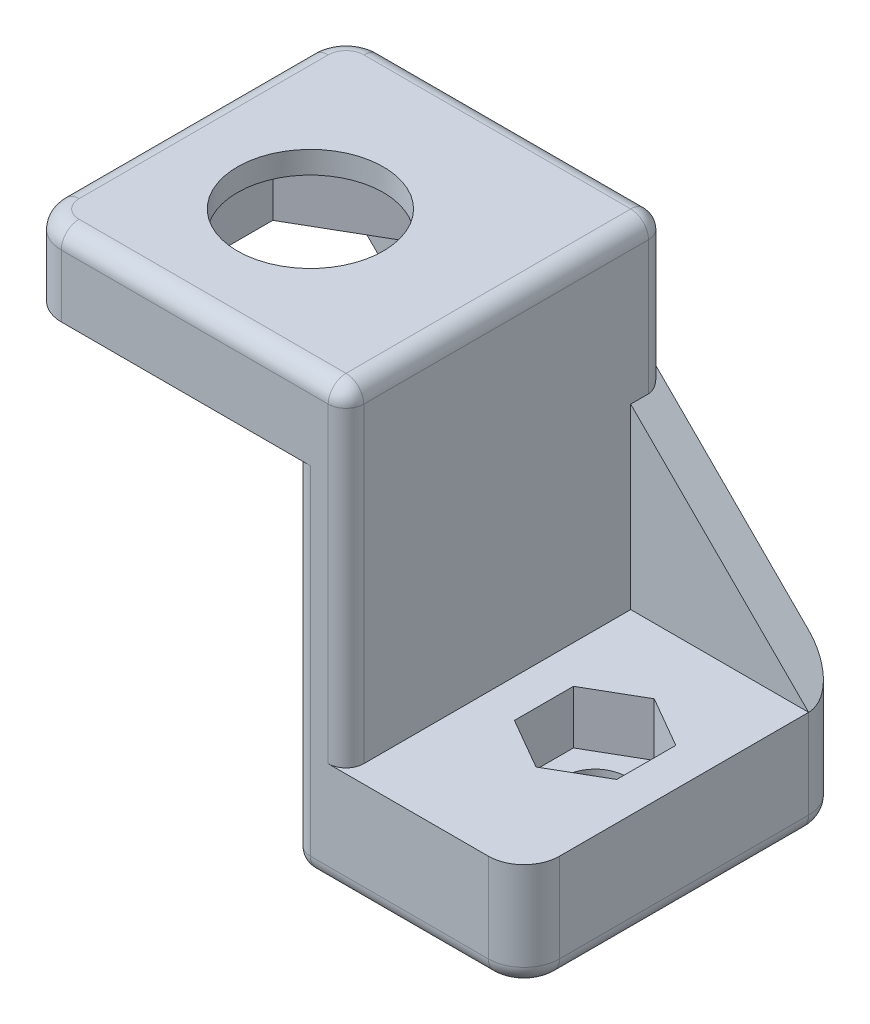
SolidWorks part; units mm, degrees
ref_plane "Front Plane" through (0, 0, 0) normal (0, 0, 1) x (1, 0, 0)
ref_plane "Top Plane" through (0, 0, 0) normal (0, 1, 0) x (1, 0, 0)
ref_plane "Right Plane" through (0, 0, 0) normal (1, 0, 0) x (0, 0, -1)
sketch "Sketch1" plane through (0, 0, 0) normal (0, 0, 1) x (1, 0, 0)
  line L0 (0, 0) -> (0, 40)
  line L1 (0, 40) -> (-30, 40)
  line L2 (-30, 40) -> (-30, 49)
  line L3 (-30, 49) -> (6, 49)
  line L4 (6, 49) -> (6, 12)
  line L5 (6, 12) -> (26, 12)
  line L6 (26, 12) -> (26, 0)
  line L7 (26, 0) -> (0, 0)
  dimension "D1" = 9
  dimension "D2" = 36
  dimension "D3" = 20
  dimension "D4" = 12
  dimension "D5" = 6
  dimension "D6" = 40
extrude "Boss-Extrude1" add sketch "Sketch1" along normal blind 36
sketch "Sketch3" plane through (0, 12, 0) normal (0, 1, 0) x (1, 0, 0)
  line L0 (16, -18) -> (26, -18) construction
  line L1 (26, -36) -> (26, 0) construction
  line L2 (16, -18) -> (6, -18) construction
  line L3 (6, -36) -> (6, 0) construction
  line L4 (16, -18) -> (16, 0) construction
  line L5 (26, 0) -> (6, 0) construction
  line L6 (16, -18) -> (16, -36) construction
  line L7 (26, -36) -> (6, -36) construction
  circle A0 centre (16, -18) radius 3.5
  dimension "D1" = 7
extrude "Cut-Extrude1" cut sketch "Sketch3" against normal blind 32
sketch "Sketch2" plane through (0, 49, 0) normal (0, 1, 0) x (1, 0, 0)
  line L0 (-30, -36) -> (-30, 0) construction
  line L3 (6, -36) -> (-30, -36) construction
  circle A0 centre (-14, -20) radius 8.2
  dimension "D1" = 16.4
  dimension "D2" = 16
  dimension "D3" = 16
extrude "Cut-Extrude2" cut sketch "Sketch2" against normal blind 32
sketch "Sketch4" plane through (0, 12, 0) normal (0, 1, 0) x (1, 0, 0)
  line L0 (26, -36) -> (26, 0) construction
  line L1 (16, -24.6395) -> (21.75, -21.3198)
  line L2 (21.75, -21.3198) -> (21.75, -14.6802)
  line L3 (21.75, -14.6802) -> (16, -11.3605)
  line L4 (16, -11.3605) -> (10.25, -14.6802)
  line L5 (10.25, -14.6802) -> (10.25, -21.3198)
  line L6 (10.25, -21.3198) -> (16, -24.6395)
  circle A0 centre (16, -18) radius 5.75 construction
  dimension "D1" = 11.5
extrude "Cut-Extrude3" cut sketch "Sketch4" against normal blind 6
sketch "Sketch5" plane through (0, 0, 0) normal (0, 0, -1) x (-1, 0, 0)
  line L0 (-26, 12) -> (-6, 32)
  line L1 (-6, 32) -> (-6, 12)
  line L2 (-6, 12) -> (-26, 12)
  line L3 (0, 10) -> (0, 40)
  line L4 (0, 40) -> (30, 40)
  line L5 (30, 40) -> (0, 10)
  line L6 (-6, 12) -> (-6, 49) construction
  line L7 (0, 40) -> (0, 0) construction
  dimension "D1" = 30
  dimension "D2" = 20
extrude "Boss-Extrude3" add sketch "Sketch5" against normal blind 4
sketch "Sketch6" plane through (0, 40, 0) normal (0, -1, 0) x (1, 0, 0)
  line L1 (-14, 8.453) -> (-4, 14.2265)
  line L2 (-4, 14.2265) -> (-4, 25.7735)
  line L3 (-4, 25.7735) -> (-14, 31.547)
  line L4 (-14, 31.547) -> (-24, 25.7735)
  line L5 (-24, 25.7735) -> (-24, 14.2265)
  line L6 (-24, 14.2265) -> (-14, 8.453)
  circle A0 centre (-14, 20) radius 10 construction
  circle A1 centre (-14, 20) radius 8.2 construction
  point P10 (0, 0)
  dimension "D1" = 20
extrude "Cut-Extrude4" cut sketch "Sketch6" against normal blind 6.5
fillet "Fillet1" radius 4 4 edges at (26, 6, 36) (26, 6, 0) (-30, 44.5, 36) (-30, 44.5, 0)
fillet "Fillet4" radius 2 15 edges at (11, 0, 36) (24.8284, 0, 34.8284) (11, 0, 0) (24.8284, 0, 1.1716) (-10, 49, 0) (-28.8284, 49, 1.1716) (-30, 49, 18) (-28.8284, 49, 34.8284) (6, 40.5, 0) (0, 20, 36) (26, 0, 18) (0, 0, 18) (-10, 49, 36) (6, 30.5, 36) (6, 49, 18)
